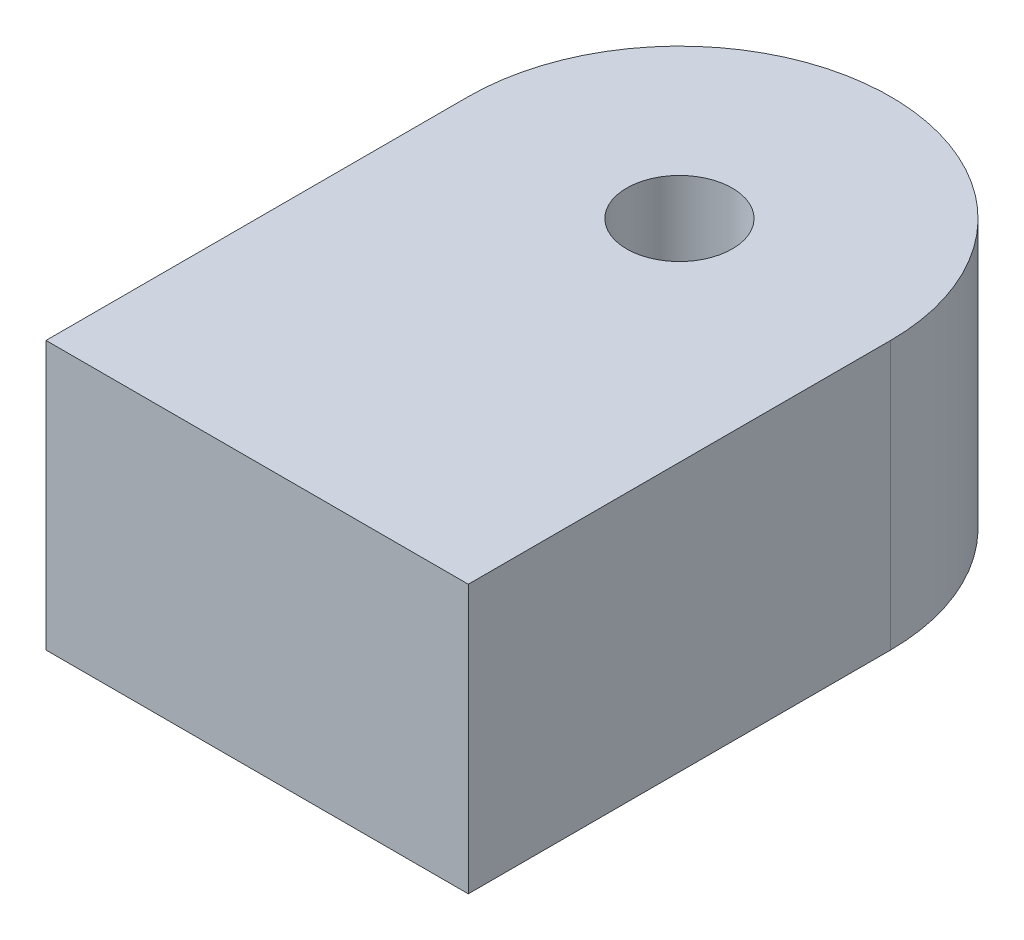
SolidWorks part; units mm, degrees
material "201 Annealed Stainless Steel (SS)"
ref_plane "Front Plane" through (0, 0, 0) normal (0, 0, 1) x (1, 0, 0)
ref_plane "Top Plane" through (0, 0, 0) normal (0, 1, 0) x (1, 0, 0)
ref_plane "Right Plane" through (0, 0, 0) normal (1, 0, 0) x (0, 0, -1)
sketch "Sketch1" plane through (0, 0, 0) normal (0, 1, 0) x (1, 0, 0)
  line L0 (-10, 0) -> (-2.5, 0) construction
  line L1 (-10, 0) -> (-10, -20)
  line L2 (-10, -20) -> (10, -20)
  line L3 (10, -20) -> (10, 0)
  line L4 (2.5, 0) -> (10, 0) construction
  arc A0 (10, 0) -> (-10, 0) centre (0, 0) ccw
  circle A1 centre (0, 0) radius 2.5
  dimension "D2" = 5
  dimension "D1" = 20
  dimension "D3" = 20
extrude "Fastener" add sketch "Sketch1" along normal blind 12.7
